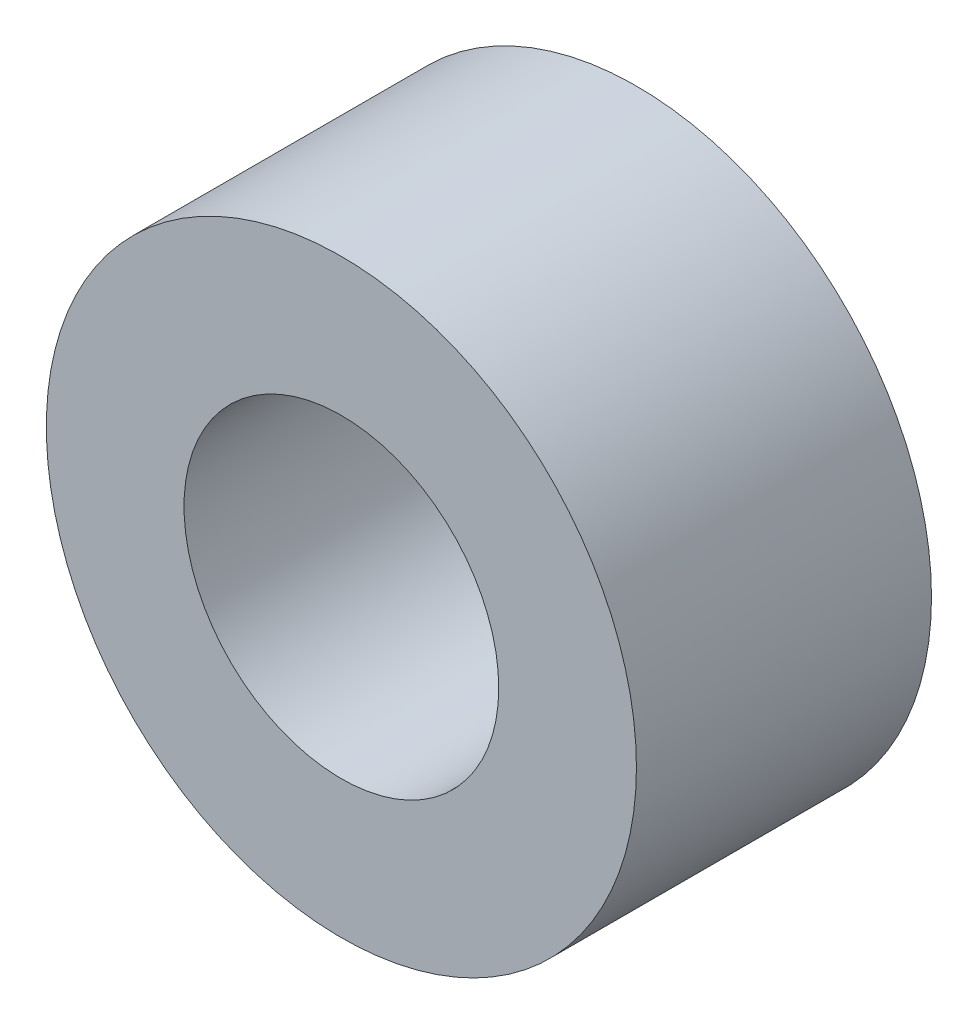
SolidWorks part; units mm, degrees
material "ABS"
ref_plane "Front Plane" through (0, 0, 0) normal (0, 0, 1) x (1, 0, 0)
ref_plane "Top Plane" through (0, 0, 0) normal (0, 1, 0) x (1, 0, 0)
ref_plane "Right Plane" through (0, 0, 0) normal (1, 0, 0) x (0, 0, -1)
sketch "Sketch1" plane through (0, 0, 0) normal (0, 0, 1) x (1, 0, 0)
  line L0 (0, 1.6) -> (0, 3) construction
  line L1 (0, -1.6) -> (0, -3) construction
  circle A0 centre (0, 0) radius 3
  circle A1 centre (0, 0) radius 1.6
  dimension "OD" = 6
  dimension "ID" = 3.2
sketch "Sketch2" plane through (0, 0, 0) normal (1, 0, 0) x (0, 0, -1)
  line L0 (-1.5, 1.6) -> (1.5, 1.6) construction
  line L1 (-1.5, -1.6) -> (1.5, -1.6) construction
  line L2 (-1.5, -3) -> (1.5, -3) construction
  line L3 (-1.5, 3) -> (1.5, 3) construction
  dimension "Length" = 3
extrude "Extrude1" add sketch "Sketch1" along normal up to vertex (1.5 mm away) and the other way up to vertex (1.5 mm away) up to point (0, 1.6, 1.5) other way up to point (0, 1.6, -1.5)
sketch "Sketch3" plane through (0, 0, 1.5) normal (0, 0, 1) x (1, 0, 0)
  circle A0 centre (0, 0) radius 1.6 construction
  circle A3 centre (0, 0) radius 1.6
  point P3 (-1.6, 0)
